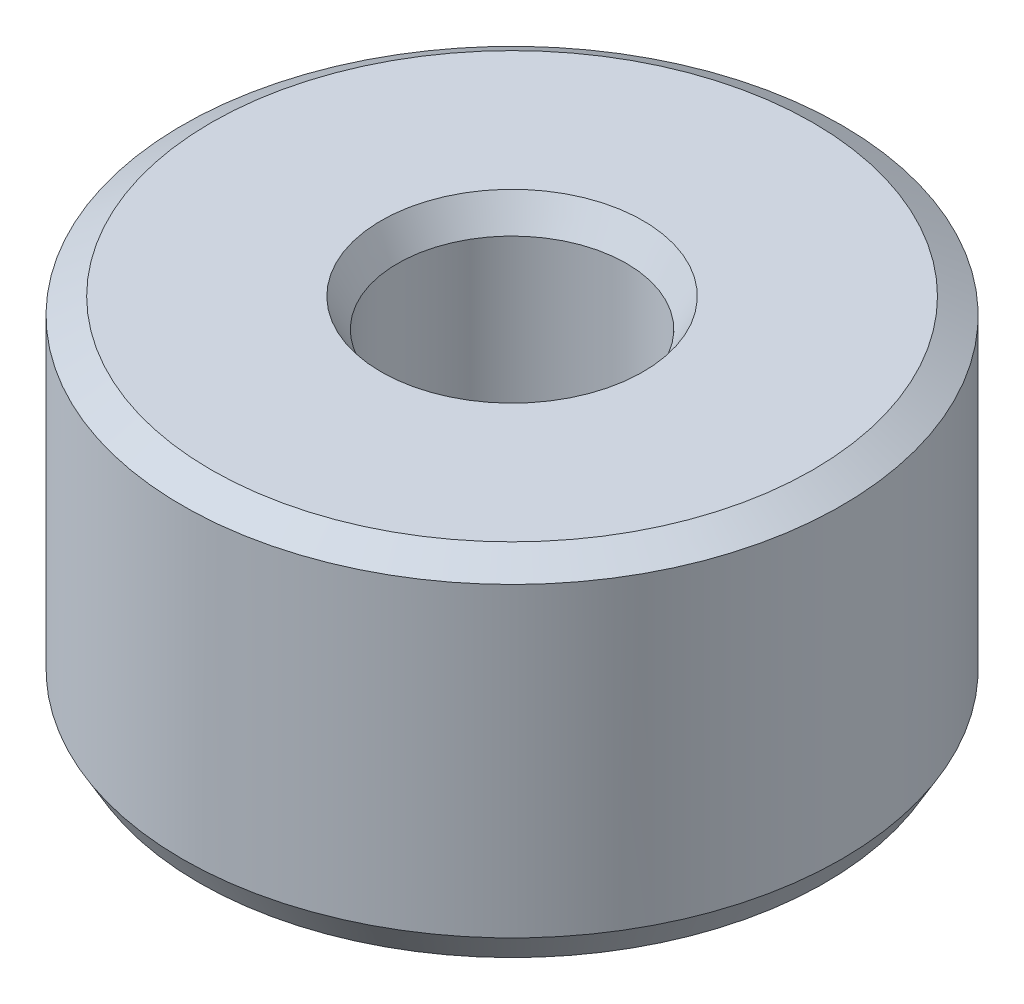
SolidWorks part; units mm, degrees
ref_plane "Front Plane" through (0, 0, 0) normal (0, 0, 1) x (1, 0, 0)
ref_plane "Top Plane" through (0, 0, 0) normal (0, 1, 0) x (1, 0, 0)
ref_plane "Right Plane" through (0, 0, 0) normal (1, 0, 0) x (0, 0, -1)
sketch "Sketch1" plane through (0, 0, 0) normal (0, 1, 0) x (1, 0, 0)
  circle A0 centre (0, 0) radius 12.5
  dimension "SLEEVE_OD" = 25
extrude "Boss-Extrude1" add sketch "Sketch1" along normal blind 13.3305
sketch "Sketch2" plane through (0, 0, 0) normal (0, 1, 0) x (1, 0, 0)
  circle A0 centre (0, 0) radius 4.3392
  dimension "BORE_D" = 8.6785
extrude "Cut-Extrude1" cut sketch "Sketch2" along normal through all
chamfer "Chamfer1" distance 0.6296 angle 60 4 edges at (0, 13.3305, 4.3392) (0, 0, 4.3392) (0, 0, 12.5) (0, 13.3305, 12.5) first distance on face at (0, 13.3305, 4.3392) first distance on face at (0, 0, 4.3392) first distance on face at (0, 13.3305, 12.5)
